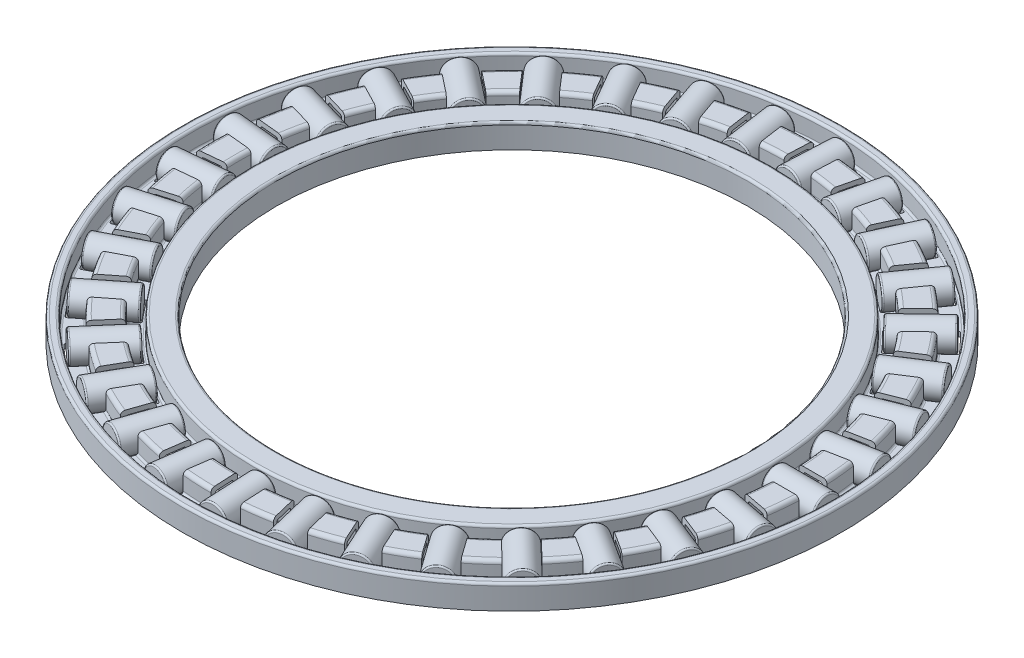
SolidWorks part; units mm, degrees
note: '?' marks a value the reader was unsure of.
material "AISI 1020"
ref_plane "Front Plane" through (0, 0, 0) normal (0, 0, 1) x (1, 0, 0)
ref_plane "Top Plane" through (0, 0, 0) normal (0, 1, 0) x (1, 0, 0)
ref_plane "Right Plane" through (0, 0, 0) normal (1, 0, 0) x (0, 0, -1)
sketch "Sketch1" plane through (0, 0, 0) normal (1, 0, 0) x (0, 0, -1)
  line L0 (-35, 0) -> (35, 0) construction
  line L1 (-25.025, 0) -> (25.025, 0) construction
  line L2 (35, -1.5) -> (35, 1.5) construction
  line L3 (25.025, -1.275) -> (25.025, 1.275) construction
  line L4 (25.025, -1.275) -> (25.85, -1.275) construction
  line L5 (25.85, -1.275) -> (25.85, 0.7792) construction
  line L6 (25.85, 0.7792) -> (26.675, 0.7792) construction
  line L7 (26.675, 0.7792) -> (26.675, -1.275) construction
  line L8 (26.675, -1.275) -> (29.5042, -1.275) construction
  line L9 (29.5042, -1.275) -> (29.5042, 0.7792) construction
  line L10 (29.5042, 0.7792) -> (31.5042, 0.7792) construction
  line L11 (31.5042, 0.7792) -> (31.5042, -1.275) construction
  line L12 (31.5042, -1.275) -> (34.3333, -1.275) construction
  line L13 (34.3333, -1.275) -> (34.3333, 0.7792) construction
  line L14 (34.3333, 0.7792) -> (34.6667, 0.7792) construction
  line L15 (25.025, 1.275) -> (27.5, 1.275) construction
  line L16 (27.5, 1.275) -> (27.5, -0.7792) construction
  line L17 (27.5, -0.7792) -> (29.0083, -0.7792) construction
  line L18 (29.0083, -0.7792) -> (29.0083, 1.275) construction
  line L19 (29.0083, 1.275) -> (32, 1.275) construction
  line L20 (32, 1.275) -> (32, -0.7792) construction
  line L21 (32, -0.7792) -> (34, -0.7792) construction
  line L22 (34, -0.7792) -> (34, 1.275) construction
  line L23 (34, 1.275) -> (35, 1.275) construction
  line L24 (29.5042, 0.7792) -> (29.0083, 0.7792) construction
  line L25 (26.675, 0.7792) -> (26.675, 1.275) construction
  line L26 (31.5042, 0.7792) -> (32, 0.7792) construction
  line L27 (27.5, -0.7792) -> (27.5, -1.275) construction
  line L28 (27.5, -0.7792) -> (26.675, -0.7792) construction
  line L29 (34.3333, 0.7792) -> (34, 0.7792) construction
  line L30 (34.6667, 0.7792) -> (34.6667, -1.275) construction
  line L31 (34.6667, -1.275) -> (35, -1.275) construction
  line L32 (0, 1.5) -> (0, -1.5) construction
  line L33 (-27.5, 1.5) -> (27.5, 1.5) construction
  line L34 (-34, 1.275) -> (34, 1.275) construction
  line L35 (34.6667, 0.7792) -> (35, 0.7792) construction
  line L36 (29.0083, -0.7792) -> (29.0083, -1.275) construction
  line L37 (31.5042, 0.7792) -> (31.5042, 1.275) construction
  line L38 (25.85, -0.7792) -> (25.025, -0.7792) construction
  line L39 (26.675, -0.7792) -> (25.85, -0.7792) construction
  point P4 (0, 0)
  point P8 (0, 0)
  point P11 (35, 0)
  point P14 (25.025, 0)
  point P45 (0, 1.5)
  point P48 (0, 0)
  point P49 (0, 1.5)
  point P55 (0, 1.275)
  dimension "OD" = 70
  dimension "ID" = 50.05
  dimension "Thickness" = 3
  dimension "Approx. Raceway Thickness" = 2.55
  dimension "Inner Raceway" = 55
  dimension "Outer Raceway" = 68
  dimension "Approx. Raceway Notch Width" = 2
  dimension "D3" = 2
sketch "Sketch2" plane through (0, 0, 0) normal (0, 1, 0) x (1, 0, 0)
  line L0 (27.5, 0) -> (34, 0) construction
  line L1 (33.675, 0) -> (27.825, 0)
  line L2 (33.6416, -1.5) -> (27.7845, -1.5)
  line L3 (33.6416, 1.5) -> (27.7845, 1.5)
  circle A0 centre (0, 0) radius 25.025
  circle A1 centre (0, 0) radius 27.5
  circle A2 centre (0, 0) radius 34
  circle A3 centre (0, 0) radius 35
  arc A4 (27.7845, -1.5) -> (27.7845, 1.5) centre (0, 0) ccw
  arc A5 (33.6416, -1.5) -> (33.6416, 1.5) centre (0, 0) ccw
  arc A6 (33.6416, 1.5) -> (33.4133, 4.1905) centre (0, 0) ccw
  point P15 (30.75, 0)
  dimension "Approx. Roller Length" = 5.85
  dimension "Roller Thickness" = 3
  dimension "Roller Arc Length" = 3.001
  dimension "Approx. Roller Gap" = 2.7009
sketch "Sketch3" plane through (0, 0, 0) normal (1, 0, 0) x (0, 0, -1)
  line L0 (25.85, -1.275) -> (25.85, 0.7792)
  line L1 (25.85, 0.7792) -> (26.675, 0.7792)
  line L2 (26.675, 0.7792) -> (26.675, -1.275)
  line L3 (26.675, -1.275) -> (29.5042, -1.275)
  line L4 (29.5042, -1.275) -> (29.5042, 0.7792)
  line L5 (29.5042, 0.7792) -> (31.5042, 0.7792)
  line L6 (31.5042, 0.7792) -> (31.5042, -1.275)
  line L7 (31.5042, -1.275) -> (34.3333, -1.275)
  line L8 (34.3333, -1.275) -> (34.3333, 0.7792)
  line L9 (34.3333, 0.7792) -> (34.6667, 0.7792)
  line L10 (34.6667, 0.7792) -> (34.6667, -1.275)
  line L11 (34.6667, -1.275) -> (35, -1.275)
  line L12 (35, -1.275) -> (35, 1.275)
  line L13 (35, 1.275) -> (34, 1.275)
  line L14 (34, 1.275) -> (34, -0.7792)
  line L15 (34, -0.7792) -> (32, -0.7792)
  line L16 (32, -0.7792) -> (32, 1.275)
  line L17 (32, 1.275) -> (29.0083, 1.275)
  line L18 (29.0083, 1.275) -> (29.0083, -0.7792)
  line L19 (29.0083, -0.7792) -> (27.5, -0.7792)
  line L20 (27.5, -0.7792) -> (27.5, 1.275)
  line L21 (27.5, 1.275) -> (25.025, 1.275)
  line L22 (25.025, 1.275) -> (25.025, -1.275)
  line L23 (25.025, -1.275) -> (25.85, -1.275)
revolve "Revolve1" add sketch "Sketch3" angle 360 about L32
fillet "Fillet1" radius 0.4 4 edges at (0, -1.275, 31.5042) (0, -1.275, 34.3333) (0, -1.275, 26.675) (0, -1.275, 29.5042)
fillet "Fillet2" radius 0.4 2 edges at (0, 1.275, 32) (0, 1.275, 29.0083)
fillet "Fillet3" radius 0.25 4 edges at (0, 1.275, 34) (0, 1.275, 35) (0, 1.275, 27.5) (0, 1.275, 25.025)
fillet "Fillet4" radius 0.2 6 edges at (0, 0.7792, 29.5042) (0, 0.7792, 31.5042) (0, -0.7792, 34) (0, -0.7792, 32) (0, -0.7792, 29.0083) (0, -0.7792, 27.5)
sketch "Sketch4" plane through (0, 0, 0) normal (0, 1, 0) x (1, 0, 0)
  line L0 (27.7845, 1.5) -> (33.6416, 1.5)
  line L1 (27.7845, -1.5) -> (33.6416, -1.5)
  arc A0 (27.7845, -1.5) -> (27.7845, 1.5) centre (0, 0) ccw construction
  arc A1 (27.7845, -1.5) -> (27.7845, 1.5) centre (0, 0) ccw
  arc A2 (33.6416, -1.5) -> (33.6416, 1.5) centre (0, 0) ccw construction
  arc A3 (33.6416, -1.5) -> (33.6416, 1.5) centre (0, 0) ccw
extrude "Cut-Extrude1" cut sketch "Sketch4" against normal through all both and the other way through all
fillet "Fillet5" radius 0.15 4 edges at (33.6416, -1.0271, -1.5) (33.6416, -1.0271, 1.5) (27.7845, -1.0271, -1.5) (27.7845, -1.0271, 1.5)
pattern_circular "CirPattern1" count 33 over 360 about axis through (0, 0, 0) along (0, 1, 0) of "Cut-Extrude1", "Fillet5"
sketch "Sketch5" plane through (0, 0, 0) normal (0, 1, 0) x (1, 0, 0)
  line L0 (27.9425, 0) -> (27.9425, 1.5)
  line L2 (27.9425, 1.5) -> (33.4978, 1.5)
  line L3 (33.4978, 1.5) -> (33.4978, 0)
  line L4 (33.4978, 0) -> (27.9425, 0)
  line L5 (33.675, 0) -> (27.825, 0) construction
revolve "Revolve2" add sketch "Sketch5" angle 360 about L1
fillet "Fillet6" radius 0.15 2 edges at (27.9425, 0, -1.5) (33.4978, 0, -1.5)
pattern_circular "CirPattern2" count 33 over 360 about axis through (0, 0, 0) along (0, 1, 0) of bodies 107
ref_axis "Center Axis 1" through (0, 1.65, 0) along (0, -1, 0)?
ref_plane "Contact Plane 1" through (0, 1.5, 0) normal (0, 1, 0) x (1, 0, 0)
ref_plane "Contact Plane 2" through (0, -1.5, 0) normal (0, 1, 0) x (1, 0, 0)
equation "\"Approx. Raceway Thickness@Sketch1\" = \"Thickness@Sketch1\" * .85"
equation "\"Approx. Raceway Notch Width@Sketch1\" =  ( \"Outer Raceway@Sketch1\" - \"Inner Raceway@Sketch1\" )  / 6.5"
equation "\"D3@Sketch1\" = \"Approx. Raceway Notch Width@Sketch1\""
equation "\"D1@Fillet2\"=\"D1@Fillet1\""
equation "\"D1@Fillet3\"=(\"OD@Sketch1\"-\"Outer Raceway@Sketch1\")/8"
equation "\"D1@Fillet1\" = \"Approx. Raceway Notch Width@Sketch1\" * 2 / 10"
equation "\"D1@Fillet4\"=\"D1@Fillet2\"/2"
equation "\"Approx. Roller Length@Sketch2\" =  ( \"Outer Raceway@Sketch1\" - \"Inner Raceway@Sketch1\" )  / 2 * .9"
equation "\"Approx. Roller Gap@Sketch2\" = \"Roller Arc Length@Sketch2\" * .9"
equation "\"Raceway Diff\"= ( \"Outer Raceway@Sketch1\" - \"Inner Raceway@Sketch1\" )"
equation "\"Circumference\"= ( \"Inner Raceway@Sketch1\" + ( \"Raceway Diff\" / 2 ) ) * 3.14"
equation "\"Instances\"= int ( \"Circumference\" /  ( \"Roller Arc Length@Sketch2\" + \"Approx. Roller Gap@Sketch2\" )  ) "
equation "\"D1@CirPattern1\"=\"Instances\""
equation "\"D1@Fillet5\" = \"Roller Arc Length@Sketch2\" / 20"
equation "\"D1@Fillet6\" = \"Roller Arc Length@Sketch2\" / 20"
equation "\"D1@CirPattern2\" = \"D1@CirPattern1\""
equation "\"Roller Thickness@Sketch2\" = \"Thickness@Sketch1\""
